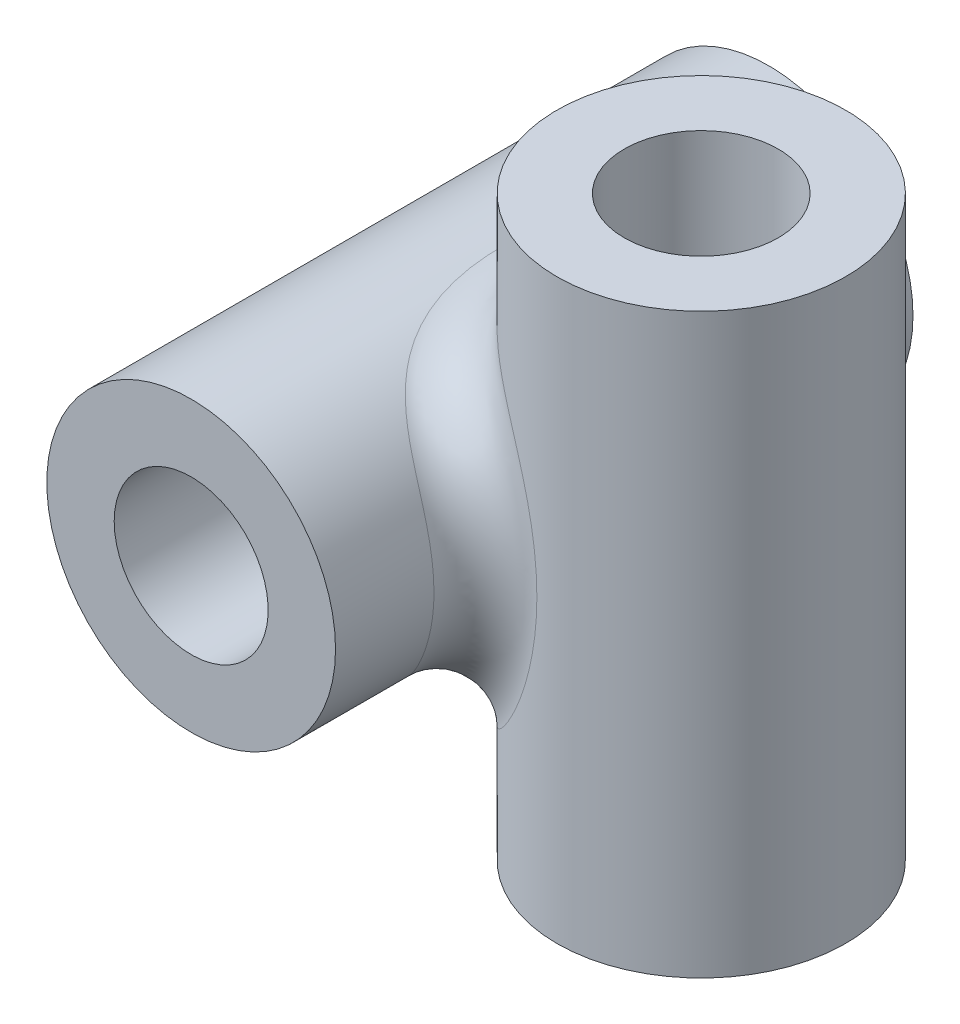
SolidWorks part; units mm, degrees
ref_plane "Front Plane" through (0, 0, 0) normal (0, 0, 1) x (1, 0, 0)
ref_plane "Top Plane" through (0, 0, 0) normal (0, 1, 0) x (1, 0, 0)
ref_plane "Right Plane" through (0, 0, 0) normal (1, 0, 0) x (0, 0, -1)
sketch "Sketch1" plane through (0, 0, 0) normal (0, 0, 1) x (1, 0, 0)
  circle A0 centre (0, 0) radius 15
  dimension "D1" = 30
extrude "Boss-Extrude1" add sketch "Sketch1" against normal mid plane 60
sketch "Sketch2" plane through (0, 0, 0) normal (0, 1, 0) x (1, 0, 0)
  circle A0 centre (23, 0) radius 15
  dimension "D1" = 30
  dimension "D2" = 23
extrude "Boss-Extrude2" add sketch "Sketch2" along normal mid plane 60
fillet "Fillet1" radius 5 1 edges at (14.6137, 3.3823, 12.4366)
hole_wizard "Hole1" positions "Sketch3" profile "Sketch4" legacy end condition through all
sketch "Sketch3" plane through (0, 30, 0) normal (0, 1, 0) x (1, 0, 0)
  point P0 (23, 0)
sketch "Sketch4" plane through (23, 30, 0) normal (1, 0, 0) x (0, 0, 1)
  line L0 (0, 0) -> (0, 60)
  line L1 (0, 60) -> (8, 60)
  line L2 (8, 60) -> (8, 0)
  line L3 (8, 0) -> (0, 0)
  line L4 (0, 110) -> (0, -10) construction
  dimension "Diameter" = 16
  dimension "Depth" = 60
hole_wizard "Hole2" positions "Sketch5" profile "Sketch6" legacy end condition through all
sketch "Sketch5" plane through (0, 0, -30) normal (0, 0, -1) x (-1, 0, 0)
  point P0 (0, 0)
sketch "Sketch6" plane through (0, 0, -30) normal (1, 0, 0) x (0, 1, 0)
  line L0 (0, 0) -> (0, 60)
  line L1 (0, 60) -> (8, 60)
  line L2 (8, 60) -> (8, 0)
  line L3 (8, 0) -> (0, 0)
  line L4 (0, 110) -> (0, -10) construction
  dimension "Diameter" = 16
  dimension "Depth" = 60
